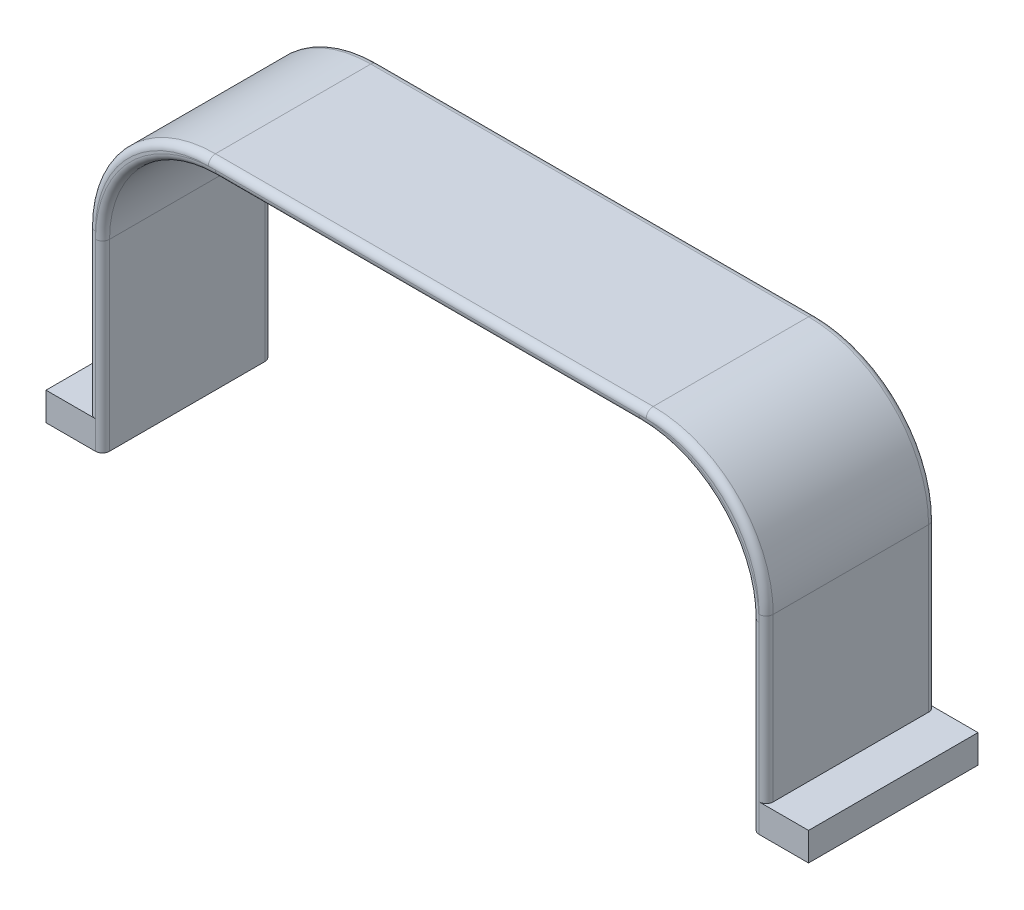
SolidWorks part; units mm, degrees
ref_plane "Front Plane" through (0, 0, 0) normal (0, 0, 1) x (1, 0, 0)
ref_plane "Top Plane" through (0, 0, 0) normal (0, 1, 0) x (1, 0, 0)
ref_plane "Right Plane" through (0, 0, 0) normal (1, 0, 0) x (0, 0, -1)
sketch "Sketch1" plane through (0, 0, 0) normal (0, 0, 1) x (1, 0, 0)
  line L0 (-67.5, 15) -> (-57.5, 15)
  line L1 (-67.5, 20) -> (-60, 20)
  line L2 (-67.5, 20) -> (-67.5, 15)
  line L4 (67.5, 20) -> (67.5, 15)
  line L5 (60, 20) -> (67.5, 20)
  line L6 (57.5, 15) -> (67.5, 15)
  line L9 (-57.5, 15) -> (-57.5, 67.5)
  line L10 (-57.5, 67.5) -> (57.5, 67.5)
  line L11 (57.5, 15) -> (57.5, 67.5)
  line L13 (-60, 20) -> (-60, 70)
  line L14 (-60, 70) -> (60, 70)
  line L15 (60, 20) -> (60, 70)
  dimension "D1" = 10
  dimension "D2" = 10
  dimension "D3" = 7.5
  dimension "D4" = 135
  dimension "D5" = 5
  dimension "D6" = 7.5
  dimension "D7" = 50
  dimension "D8" = 2.5
extrude "Boss-Extrude1" add sketch "Sketch1" along normal blind 30
fillet "Fillet3" radius 20 2 edges at (57.5, 67.5, 15) (-57.5, 67.5, 15)
fillet "Fillet4" radius 21.25 2 edges at (60, 70, 15) (-60, 70, 15)
fillet "Fillet5" radius 1.25 20 edges at (60, 34.375, 0) (53.776, 63.776, 0) (-60, 34.375, 0) (-53.776, 63.776, 0) (-57.5, 31.25, 0) (-51.6421, 61.6421, 0) (57.5, 31.25, 0) (51.6421, 61.6421, 0) (60, 34.375, 30) (53.776, 63.776, 30) (-60, 34.375, 30) (-53.776, 63.776, 30) (-57.5, 31.25, 30) (-51.6421, 61.6421, 30) (57.5, 31.25, 30) (51.6421, 61.6421, 30) (0, 70, 0) (0, 67.5, 0) (0, 70, 30) (0, 67.5, 30)
